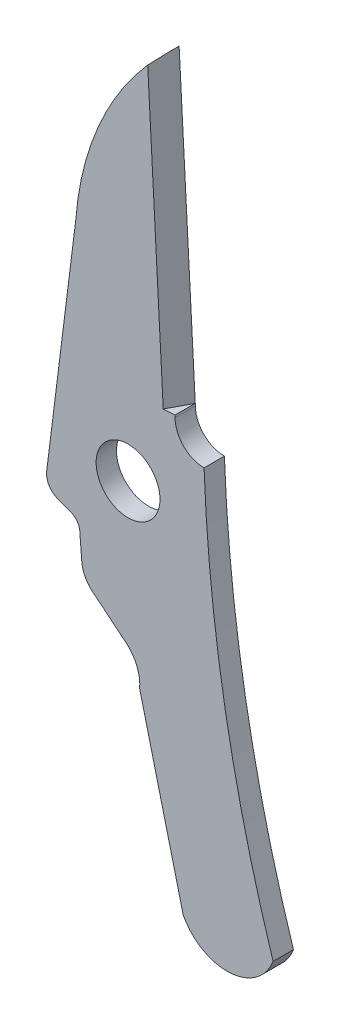
SolidWorks part; units mm, degrees
material "AISI 4340 Steel, normalized"
ref_plane "Front Plane" through (0, 0, 0) normal (0, 0, 1) x (1, 0, 0)
ref_plane "Top Plane" through (0, 0, 0) normal (0, 1, 0) x (1, 0, 0)
ref_plane "Right Plane" through (0, 0, 0) normal (1, 0, 0) x (0, 0, -1)
sketch "Sketch1" plane through (0, 0, 0) normal (0, 0, 1) x (1, 0, 0)
  line L0 (-34.2684, 6.7209) -> (42.5577, -21.2415) construction
  line L1 (8.8502, 21.404) -> (9.5614, 8.1198)
  line L2 (8.012, -2.9292) -> (9.917, -10.5492)
  line L3 (6.0816, -0.3892) -> (7.25, -1.3544)
  line L4 (5.3958, 1.6682) -> (5.472, 0.703)
  line L5 (4.4052, 2.481) -> (4.8624, 2.3032)
  line L6 (5.218, 13.4538) -> (3.948, 3.3192)
  arc A0 (9.5614, 8.1198) -> (10.8314, 6.8498) centre (10.8314, 8.1198) ccw
  arc A1 (10.8314, 6.8498) -> (13.854, -10.346) centre (75.0476, 9.2739) ccw
  arc A3 (13.854, -10.346) -> (9.917, -10.5492) centre (11.84, -9.5679) cw
  arc A4 (8.012, -2.9292) -> (7.25, -1.3544) centre (6.3169, -2.7777) ccw
  arc A5 (5.472, 0.703) -> (6.0816, -0.3892) centre (6.8427, 0.7518) ccw
  arc A6 (4.8624, 2.3032) -> (5.3958, 1.6682) centre (4.7511, 1.6682) cw
  arc A7 (3.948, 3.3192) -> (4.4052, 2.481) centre (4.698, 3.1845) ccw
  arc A8 (8.8502, 21.404) -> (5.218, 13.4538) centre (17.8801, 12.4736) ccw
  circle A9 centre (7.504, 4.6908) radius 1.397
  point P6 (11.5164, -9.9346)
  point P26 (8.6978, -10.1662)
  point P29 (0, 0)
  point P32 (11.0574, -10.9017)
  point P33 (0, 0)
  point P34 (11.9339, -11.745)
  point P35 (13.8766, -10.348)
  point P36 (13.4997, -10.348)
  point P38 (0, 0)
  point P39 (14.1702, -9.9346)
  point P41 (13.974, -10.4905)
  dimension "D1" = 2.794
  dimension "D3" = 3.556
  dimension "D5" = 2.286
  dimension "D6" = 16.7132
  dimension "D9" = 2.0574
  dimension "D12" = 3.3274
  dimension "D13" = 1.27
  dimension "D14" = 2.159
  dimension "D15" = 15.0368
  dimension "D8" = 12.7
  dimension "D16" = 64.262
  dimension "D18" = 3.0988
  dimension "D19" = 0.762
  dimension "D22" = 3.0226
  dimension "D23" = 2.1082
  dimension "D25" = 3.9878
  dimension "D27" = 1.4224
  dimension "D28" = 1.3716
  dimension "D30" = 0.254
  dimension "D31" = 1.7018
  dimension "D33" = 0.508
  dimension "D34" = 15.24
  dimension "D35" = 2.413
  dimension "D2" = 1.3716
  dimension "D4" = 8.763
  dimension "D7" = 1.3462
  dimension "D10" = 3.429
  dimension "D11" = 2.159
  dimension "D17" = 2.2098
  dimension "D20" = 2.3876
  dimension "D21" = 2.6416
  dimension "D24" = 2.032
  dimension "D26" = 5.08
  dimension "D29" = 6.0452
  dimension "D32" = 7.62
  dimension "D36" = 6.35
extrude "Boss-Extrude1" add sketch "Sketch1" along normal mid plane 0.889
ref_plane "Plane1" through (-1.2937, 24.1653, 0) normal (-0.0535, 0.9986, 0) x (0.9986, 0.0535, 0)
sketch "Sketch2" plane through (-1.2937, 24.1653, 0) normal (-0.0535, 0.9986, 0) x (0.9986, 0.0535, 0)
  line L0 (9.9818, 0.4445) -> (9.9818, -0.4445)
  line L1 (9.9818, -0.4445) -> (9.4685, -0.4445)
  line L2 (9.4685, -0.4445) -> (9.9818, 0.4445)
  dimension "D1" = 30
extrude "Cut-Extrude4" cut sketch "Sketch2" against normal blind 16.51
